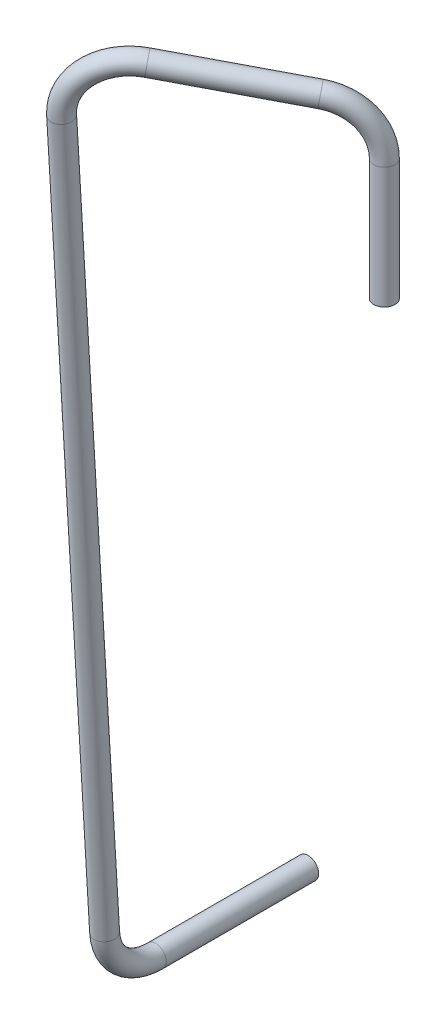
SolidWorks part; units mm, degrees
ref_plane "Piano frontale" through (0, 0, 0) normal (0, 0, 1) x (1, 0, 0)
ref_plane "Piano superiore" through (0, 0, 0) normal (0, 1, 0) x (1, 0, 0)
ref_plane "Piano destro" through (0, 0, 0) normal (1, 0, 0) x (0, 0, -1)
sketch3d "Schizzo3D1"
  line L0 (0, 0, 0) -> (0, 18.1274, 0)
  line L1 (-5.2438, 26.036, 4.32) -> (-19.4494, 28.8426, 16.0229)
  line L2 (-27.1915, 20.7587, 21.0853) -> (-32.3109, -93.4564, 9.5323)
  line L3 (-32.6332, -100.6449, 1.5728) -> (-32.6332, -100.6449, -21.2228)
  arc A0 (0, 18.1274, 0) -> (-5.2438, 26.036, 4.32) centre (-6.1745, 18.1274, 5.0867) ccw
  arc A1 (-19.4494, 28.8426, 16.0229) -> (-27.1915, 20.7587, 21.0853) centre (-20.9224, 20.9799, 16.1205) ccw
  arc A2 (-32.3109, -93.4564, 9.5323) -> (-32.6332, -100.6449, 1.5728) centre (-32.2749, -92.6529, 1.5728) ccw
  point P12 (0, 25, 0)
  point P14 (-1.0878, 18.1274, 11.2613)
  point P17 (-26.7644, 30.2878, 22.0492)
  point P18 (-15.9655, 20.1285, 22.3417)
  point P21 (-32.6332, -100.6449, 8.8052)
  point P22 (-24.283, -93.0111, 1.5728)
  dimension "D2" = 8
  dimension "D1" = 25
sweep "Sweep-Sottile2" add path "Schizzo3D1" circular profile diameter 3.17 parameters "D1"=0.5, "D3"=3.17
